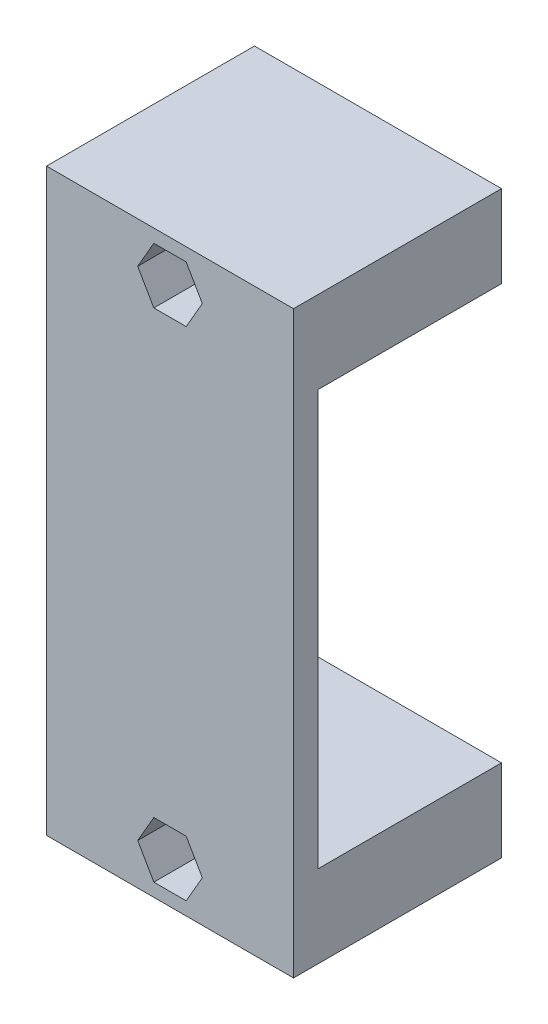
SolidWorks part; units mm, degrees
material "ABS"
ref_plane "Front Plane" through (0, 0, 0) normal (0, 0, 1) x (1, 0, 0)
ref_plane "Top Plane" through (0, 0, 0) normal (0, 1, 0) x (1, 0, 0)
ref_plane "Right Plane" through (0, 0, 0) normal (1, 0, 0) x (0, 0, -1)
sketch "Sketch2" plane through (0, 0, 0) normal (0, 0, 1) x (1, 0, 0)
  line L0 (69, -22) -> (-75.5, -22) construction
  line L1 (-37.5, -32) -> (-7.5, -32)
  line L2 (-37.5, -32) -> (-37.5, 38.4)
  line L3 (-37.5, 38.4) -> (-7.5, 38.4)
  line L4 (-7.5, -32) -> (-7.5, 38.4)
  line L5 (-37.5, -32) -> (-7.5, 38.4) construction
  line L6 (-37.5, 38.4) -> (-7.5, -32) construction
  line L7 (-75.5, 28.4) -> (69, 28.4) construction
  line L8 (-75.5, -22) -> (-75.5, 28.4) construction
  line L9 (-37.5, -22) -> (-7.5, -22) construction
  line L10 (-7.5, -22) -> (-7.5, 28.4) construction
  line L11 (-7.5, 28.4) -> (-37.5, 28.4) construction
  line L12 (-22.5, -32) -> (-22.5, -22) construction
  line L14 (-22.5, 28.4) -> (-22.5, 38.4) construction
  circle A0 centre (-22.5, -27) radius 2
  circle A1 centre (-22.5, 33.4) radius 2
  point P4 (-22.5, 3.2)
  line M7 (69, 28.4) -> (-75.5, 28.4)
  line M9 (-75.5, -22) -> (69, -22)
  dimension "D5" = 4
  dimension "D6" = 4
  dimension "D1" = 10
  dimension "D2" = 10
  dimension "D3" = 38
  dimension "D4" = 30
extrude "Boss-Extrude1" add sketch "Sketch2" along normal blind 3
extrude "Boss-Extrude2" add sketch "Sketch2<2>" against normal up to surface (22.26 mm away) contours L1 L4 L2 A0 M9 | L4 L3 L2 A1 M7 region at (-37.1838, -27, 0) region at (-37.1838, 33.4, 0)
sketch "Sketch2<2>" plane through (0, 0, 0) normal (0, 0, 1) x (1, 0, 0) same geometry as "Sketch2"
sketch "Sketch3" plane through (0, 0, 3) normal (0, 0, 1) x (1, 0, 0)
  line L1 (-24.463, 30) -> (-20.537, 30)
  line L2 (-20.537, 30) -> (-18.574, 33.4)
  line L3 (-18.574, 33.4) -> (-20.537, 36.8)
  line L4 (-20.537, 36.8) -> (-24.463, 36.8)
  line L5 (-24.463, 36.8) -> (-26.426, 33.4)
  line L6 (-26.426, 33.4) -> (-24.463, 30)
  line L7 (-20.537, -30.4) -> (-18.574, -27)
  line L8 (-18.574, -27) -> (-20.537, -23.6)
  line L9 (-20.537, -23.6) -> (-24.463, -23.6)
  line L10 (-24.463, -23.6) -> (-26.426, -27)
  line L11 (-26.426, -27) -> (-24.463, -30.4)
  line L12 (-24.463, -30.4) -> (-20.537, -30.4)
  circle A0 centre (-22.5, 33.4) radius 3.4 construction
  circle A1 centre (-22.5, -27) radius 3.4 construction
  dimension "D1" = 6.8
  dimension "D2" = 6.8
extrude "Cut-Extrude1" cut sketch "Sketch3" against normal blind 14
